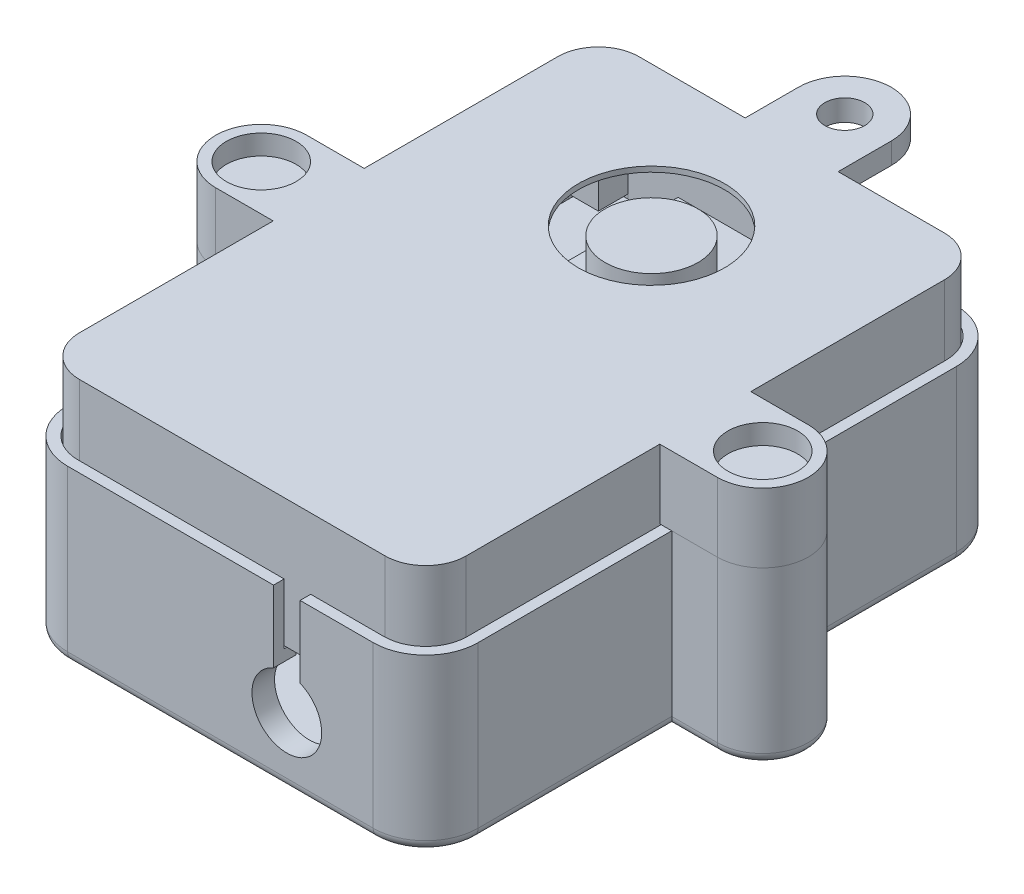
SolidWorks part; units mm, degrees
other "ESP32 Cam"
other "Front Lid"
other "Rear Lid"
ref_plane "Front Plane" through (0, 0, 0) normal (0, 0, 1) x (1, 0, 0)
ref_plane "Top Plane" through (0, 0, 0) normal (0, 1, 0) x (1, 0, 0)
ref_plane "Right Plane" through (0, 0, 0) normal (1, 0, 0) x (0, 0, -1)
sketch "Sketch1" plane through (0, 0, 0) normal (0, 1, 0) x (1, 0, 0)
  line L1 (-11.5, 20) -> (11.5, 20)
  line L2 (-13.5, 18) -> (-13.5, -18)
  line L3 (-11.5, -20) -> (11.5, -20)
  line L4 (13.5, 18) -> (13.5, -18)
  line L5 (-13.5, 20) -> (13.5, -20) construction
  line L6 (-13.5, -20) -> (13.5, 20) construction
  arc A0 (-11.5, 20) -> (-13.5, 18) centre (-11.5, 18) ccw
  arc A1 (11.5, 20) -> (13.5, 18) centre (11.5, 18) cw
  arc A2 (11.5, -20) -> (13.5, -18) centre (11.5, -18) ccw
  arc A3 (-13.5, -18) -> (-11.5, -20) centre (-11.5, -18) ccw
  point P0 (0, 0)
  dimension "D3" = 2
  dimension "D1" = 27
  dimension "D2" = 40
extrude "Boss-Extrude1" add sketch "Sketch1" along normal blind 1
sketch "Sketch2" plane through (0, 1, 0) normal (0, 1, 0) x (1, 0, 0)
  line L0 (0, 0) -> (0, 20) construction
  line L1 (11.5, 20) -> (-11.5, 20) construction
  line L3 (-7.5, 20) -> (7.5, 20)
  line L4 (-7.5, 20) -> (-7.5, 5)
  line L5 (-7.5, 5) -> (7.5, 5)
  line L6 (7.5, 20) -> (7.5, 5)
  line L7 (-7.5, 20) -> (7.5, 5) construction
  line L8 (-7.5, 5) -> (7.5, 20) construction
  point P5 (0, 12.5)
  dimension "D1" = 15
extrude "Boss-Extrude2" add sketch "Sketch2" along normal blind 2
sketch "Sketch3" plane through (0, 3, 0) normal (0, 1, 0) x (1, 0, 0)
  line L0 (0, 5) -> (0, 20) construction
  line L1 (-7.5, 5) -> (7.5, 5) construction
  line L2 (7.5, 20) -> (-7.5, 20) construction
  circle A0 centre (0, 10.5) radius 3.5
  dimension "D1" = 7
  dimension "D2" = 5.5
extrude "Lens Position" add sketch "Sketch3" along normal blind 6
sketch "Sketch5" plane through (0, 1, 0) normal (0, 1, 0) x (1, 0, 0)
  line L0 (-11.5, -20) -> (11.5, -20) construction
  line L1 (10, -8) -> (13, -8)
  line L2 (10, -8) -> (10, -11)
  line L3 (10, -11) -> (13, -11)
  line L4 (13, -8) -> (13, -11)
  line L5 (10, -8) -> (13, -11) construction
  line L6 (10, -11) -> (13, -8) construction
  line L7 (13.5, -18) -> (13.5, 18) construction
  point P0 (11.5, -9.5)
  dimension "D1" = 3
  dimension "D2" = 10.5
  dimension "D3" = 2
extrude "Boss-Extrude4" add sketch "Sketch5" along normal blind 1
sketch "Sketch6" plane through (0, 9, 0) normal (0, 1, 0) x (1, 0, 0)
  line L37 (7.5, 21.05) -> (-7.5, 21.05)
  line L38 (-7.5, 21.05) -> (-11.5, 21.05)
  line L39 (-14.55, 18) -> (-14.55, -18)
  line L40 (-11.5, -21.05) -> (11.5, -21.05)
  line L41 (14.55, -18) -> (14.55, 18)
  line L42 (11.5, 21.05) -> (7.5, 21.05)
  line L43 (7.5, 20.25) -> (-7.5, 20.25)
  line L44 (11.5, 20.25) -> (7.5, 20.25)
  line L45 (13.75, -18) -> (13.75, 18)
  line L46 (-11.5, -20.25) -> (11.5, -20.25)
  line L47 (-13.75, 18) -> (-13.75, -18)
  line L48 (-7.5, 20.25) -> (-11.5, 20.25)
  line L55 (7.5, 20.25) -> (-7.5, 20.25) construction
  line L56 (11.5, 20.25) -> (7.5, 20.25) construction
  line L57 (13.75, -18) -> (13.75, 18) construction
  line L58 (-11.5, -20.25) -> (11.5, -20.25) construction
  line L59 (-13.75, 18) -> (-13.75, -18) construction
  line L60 (-7.5, 20.25) -> (-11.5, 20.25) construction
  circle A6 centre (0, 10.5) radius 5.5
  circle A8 centre (0, 10.5) radius 5.5
  arc A36 (-11.5, 21.05) -> (-14.55, 18) centre (-11.5, 18) ccw
  arc A37 (-14.55, -18) -> (-11.5, -21.05) centre (-11.5, -18) ccw
  arc A38 (11.5, -21.05) -> (14.55, -18) centre (11.5, -18) ccw
  arc A39 (14.55, 18) -> (11.5, 21.05) centre (11.5, 18) ccw
  arc A40 (13.75, 18) -> (11.5, 20.25) centre (11.5, 18) ccw
  arc A41 (11.5, -20.25) -> (13.75, -18) centre (11.5, -18) ccw
  arc A42 (-13.75, -18) -> (-11.5, -20.25) centre (-11.5, -18) ccw
  arc A43 (-11.5, 20.25) -> (-13.75, 18) centre (-11.5, 18) ccw
  arc A44 (13.75, 18) -> (11.5, 20.25) centre (11.5, 18) ccw construction
  arc A45 (11.5, -20.25) -> (13.75, -18) centre (11.5, -18) ccw construction
  arc A46 (-13.75, -18) -> (-11.5, -20.25) centre (-11.5, -18) ccw construction
  arc A47 (-11.5, 20.25) -> (-13.75, 18) centre (-11.5, 18) ccw construction
  dimension "D1" = 0.25
  dimension "D2" = 0.8
  dimension "D3" = 2
extrude "Lens Opening" add sketch "Sketch6" along normal blind 0.4 from offset 0.25 separate body
sketch "Sketch8" plane through (0, 9.25, 0) normal (0, -1, 0) x (1, 0, 0)
  line L4 (-11.5, -21.05) -> (11.5, -21.05)
  line L5 (14.55, -18) -> (14.55, 18)
  line L6 (11.5, 21.05) -> (-11.5, 21.05)
  line L7 (-14.55, 18) -> (-14.55, -18)
  line L8 (-11.5, -21.05) -> (11.5, -21.05)
  line L9 (14.55, -18) -> (14.55, 18)
  line L10 (11.5, 21.05) -> (-11.5, 21.05)
  line L11 (-14.55, 18) -> (-14.55, -18)
  line L16 (-11.5, -20.25) -> (11.5, -20.25)
  line L17 (13.75, -18) -> (13.75, 18)
  line L18 (11.5, 20.25) -> (-11.5, 20.25)
  line L19 (-13.75, 18) -> (-13.75, -18)
  line L20 (-11.5, -20.25) -> (11.5, -20.25)
  line L21 (13.75, -18) -> (13.75, 18)
  line L22 (11.5, 20.25) -> (-11.5, 20.25)
  line L23 (-13.75, 18) -> (-13.75, -18)
  arc A4 (11.5, -21.05) -> (14.55, -18) centre (11.5, -18) ccw
  arc A5 (14.55, 18) -> (11.5, 21.05) centre (11.5, 18) ccw
  arc A6 (-11.5, 21.05) -> (-14.55, 18) centre (-11.5, 18) ccw
  arc A7 (-14.55, -18) -> (-11.5, -21.05) centre (-11.5, -18) ccw
  arc A8 (11.5, -21.05) -> (14.55, -18) centre (11.5, -18) ccw
  arc A9 (14.55, 18) -> (11.5, 21.05) centre (11.5, 18) ccw
  arc A10 (-11.5, 21.05) -> (-14.55, 18) centre (-11.5, 18) ccw
  arc A11 (-14.55, -18) -> (-11.5, -21.05) centre (-11.5, -18) ccw
  arc A16 (11.5, -20.25) -> (13.75, -18) centre (11.5, -18) ccw
  arc A17 (13.75, 18) -> (11.5, 20.25) centre (11.5, 18) ccw
  arc A18 (-11.5, 20.25) -> (-13.75, 18) centre (-11.5, 18) ccw
  arc A19 (-13.75, -18) -> (-11.5, -20.25) centre (-11.5, -18) ccw
  arc A20 (11.5, -20.25) -> (13.75, -18) centre (11.5, -18) ccw
  arc A21 (13.75, 18) -> (11.5, 20.25) centre (11.5, 18) ccw
  arc A22 (-11.5, 20.25) -> (-13.75, 18) centre (-11.5, 18) ccw
  arc A23 (-13.75, -18) -> (-11.5, -20.25) centre (-11.5, -18) ccw
  dimension "D1" = 0
  dimension "D2" = 0.8
extrude "Boss-Extrude7" add sketch "Sketch8" along normal up to vertex (9.25 mm away) up to point (-11.5, 0, 20)
sketch "Sketch9" plane through (0, 9.25, 0) normal (0, -1, 0) x (1, 0, 0)
  line L0 (13.75, 18) -> (11.5, 18)
  line L1 (11.5, 18) -> (11.5, 20.25)
  line L2 (4.95, 0) -> (-4.95, 0) construction
  line L3 (11.5, -18) -> (11.5, -20.25)
  line L4 (13.75, -18) -> (11.5, -18)
  line L5 (0, -4.95) -> (0, 4.95) construction
  line L6 (-13.75, -18) -> (-11.5, -18)
  line L7 (-11.5, -18) -> (-11.5, -20.25)
  line L8 (-11.5, 18) -> (-11.5, 20.25)
  line L9 (-13.75, 18) -> (-11.5, 18)
  arc A0 (13.75, 18) -> (11.5, 20.25) centre (11.5, 18) ccw construction
  arc A1 (13.75, 18) -> (11.5, 20.25) centre (11.5, 18) ccw
  arc A2 (13.75, -18) -> (11.5, -20.25) centre (11.5, -18) cw
  arc A3 (-13.75, -18) -> (-11.5, -20.25) centre (-11.5, -18) ccw
  arc A4 (-13.75, 18) -> (-11.5, 20.25) centre (-11.5, 18) cw
extrude "Boss-Extrude9" add sketch "Sketch9" along normal offset from surface (8.15 mm away) 0.1 up to face at (0, 1, -4.1667)
sketch "Sketch11" plane through (0, 9.65, 0) normal (0, 1, 0) x (1, 0, 0)
  line L1 (13.75, -7.6) -> (9.6, -7.6)
  line L2 (9.6, -7.6) -> (9.6, -11.4)
  line L3 (9.6, -11.4) -> (13.75, -11.4)
  line L4 (13, -11) -> (13, -8)
  line L5 (13, -8) -> (10, -8)
  line L6 (10, -8) -> (10, -11)
  line L7 (10, -11) -> (13, -11)
  line L8 (13, -11) -> (13, -8) construction
  line L9 (13, -8) -> (10, -8) construction
  line L10 (10, -8) -> (10, -11) construction
  line L11 (10, -11) -> (13, -11) construction
  line L12 (13.75, 18) -> (13.75, -18) construction
  line L13 (13.75, -7.6) -> (13.75, -11.4)
  line L14 (9.6, -11.4) -> (13.4, -11.4) construction
  line L15 (13.4, -11.4) -> (13.4, -7.6) construction
  line L16 (13.4, -7.6) -> (9.6, -7.6) construction
  dimension "D1" = 0
  dimension "D2" = 0.4
extrude "Cut-Extrude1" [suppressed] cut sketch "Sketch11" against normal up to vertex
sketch "Sketch12" plane through (0, 0, 0) normal (0, -1, 0) x (1, 0, 0)
  line L0 (0, 0) -> (0, 20) construction
  line L1 (-11.5, 20) -> (11.5, 20) construction
  line L3 (9.375, -5.65) -> (-9.375, -5.65)
  line L4 (9.375, -5.65) -> (9.375, 20)
  line L5 (9.375, 20) -> (-9.375, 20)
  line L6 (-9.375, -5.65) -> (-9.375, 20)
  line L7 (9.375, -5.65) -> (-9.375, 20) construction
  line L8 (9.375, 20) -> (-9.375, -5.65) construction
  point P5 (0, 7.175)
  dimension "D1" = 18.75
  dimension "D2" = 25.65
extrude "Boss-Extrude10" add sketch "Sketch12" along normal blind 0.75
sketch "Sketch13" plane through (0, -0.75, 0) normal (0, -1, 0) x (1, 0, 0)
  line L0 (0, -5.65) -> (0, 20) construction
  line L1 (-9.375, -5.65) -> (9.375, -5.65) construction
  line L2 (8, 12.35) -> (2, 12.35) construction
  line L3 (2, 12.35) -> (-8, 12.35)
  line L4 (8, 9.35) -> (8, -5.15)
  line L5 (8, -5.15) -> (-8, -5.15)
  line L6 (-8, 12.35) -> (-8, -5.15)
  line L7 (8, 12.35) -> (-8, -5.15) construction
  line L8 (8, -5.15) -> (-8, 12.35) construction
  line L11 (8, 9.35) -> (2, 9.35)
  line L12 (2, 12.35) -> (2, 9.35)
  line L13 (8, 12.35) -> (8, 9.35) construction
  line L14 (9.375, 20) -> (11.5, 20) construction
  point P5 (0, 3.6)
  dimension "D1" = 16
  dimension "D2" = 17.5
  dimension "D3" = 3
  dimension "D4" = 6
  dimension "D5" = 0.5
extrude "Boss-Extrude11" add sketch "Sketch13" along normal blind 2.3
sketch "Sketch14" plane through (0, 0, 0) normal (0, -1, 0) x (1, 0, 0)
  line L0 (9.375, 20) -> (11.5, 20) construction
  line L1 (12.75, -16.2) -> (10.25, -16.2)
  line L2 (12.75, -16.2) -> (12.75, 4)
  line L3 (12.75, 4) -> (10.25, 4)
  line L4 (10.25, -16.2) -> (10.25, 4)
  line L5 (12.75, -16.2) -> (10.25, 4) construction
  line L6 (12.75, 4) -> (10.25, -16.2) construction
  line L7 (13.5, 18) -> (13.5, -18) construction
  point P0 (11.5, -6.1)
  dimension "D1" = 20.2
  dimension "D2" = 2.5
  dimension "D3" = 16
  dimension "D4" = 0.75
extrude "Boss-Extrude12" add sketch "Sketch14" along normal blind 2.45
sketch "Sketch16" plane through (0, -2.45, 0) normal (0, -1, 0) x (1, 0, 0)
  line L0 (11.5, 4) -> (11.5, -16.2) construction
  line L3 (11.2, 3) -> (11.8, 3)
  line L8 (11.2, 3) -> (11.2, 2.4)
  line L9 (11.2, 2.4) -> (11.8, 2.4)
  line L10 (11.8, 3) -> (11.8, 2.4)
  line L11 (12.75, 4) -> (10.25, 4) construction
  line L12 (10.25, -16.2) -> (12.75, -16.2) construction
  dimension "D1" = 0.6
  dimension "D2" = 1
extrude "Boss-Extrude14" add sketch "Sketch16" along normal blind 5.5
pattern_linear "LPattern1" count 8 spacing 2.5 along (0, 0, -1) of "Boss-Extrude14"
sketch "Sketch17" plane through (0, -3.05, 0) normal (0, -1, 0) x (1, 0, 0)
  line L14 (-11.5, -21.95) -> (11.5, -21.95)
  line L15 (15.45, -18) -> (15.45, 18)
  line L16 (-11.5, -21.15) -> (11.5, -21.15)
  line L17 (-14.65, 18) -> (-14.65, -18)
  line L18 (11.5, 21.15) -> (-11.5, 21.15)
  line L19 (-11.5, -21.15) -> (11.5, -21.15)
  line L20 (-14.65, 18) -> (-14.65, -18)
  line L21 (11.5, 21.15) -> (-11.5, 21.15)
  line L22 (14.65, -18) -> (14.65, 18)
  line L23 (11.5, 21.95) -> (-11.5, 21.95)
  line L24 (-15.45, 18) -> (-15.45, -18)
  arc A16 (11.5, -21.95) -> (15.45, -18) centre (11.5, -18) ccw
  arc A17 (15.45, 18) -> (11.5, 21.95) centre (11.5, 18) ccw
  arc A18 (-11.5, 21.95) -> (-15.45, 18) centre (-11.5, 18) ccw
  arc A19 (-15.45, -18) -> (-11.5, -21.95) centre (-11.5, -18) ccw
  arc A20 (11.5, -21.15) -> (14.65, -18) centre (11.5, -18) ccw
  arc A21 (-14.65, -18) -> (-11.5, -21.15) centre (-11.5, -18) ccw
  arc A22 (-11.5, 21.15) -> (-14.65, 18) centre (-11.5, 18) ccw
  arc A23 (14.65, 18) -> (11.5, 21.15) centre (11.5, 18) ccw
  arc A24 (11.5, -21.15) -> (14.65, -18) centre (11.5, -18) ccw
  arc A25 (-14.65, -18) -> (-11.5, -21.15) centre (-11.5, -18) ccw
  arc A26 (-11.5, 21.15) -> (-14.65, 18) centre (-11.5, 18) ccw
  arc A27 (14.65, 18) -> (11.5, 21.15) centre (11.5, 18) ccw
  dimension "D1" = 0.1
  dimension "D2" = 0.8
extrude "Boss-Extrude15" add sketch "Sketch17" against normal blind 12.5 from offset 5 separate body
sketch "Sketch18" plane through (0, -8.05, 0) normal (0, -1, 0) x (1, 0, 0)
  line L0 (-11.5, -20.25) -> (11.5, -20.25) construction
  line L1 (-13.75, 18) -> (-13.75, -18) construction
  line L2 (13.75, -18) -> (13.75, 18) construction
  line L3 (11.5, 20.25) -> (-11.5, 20.25) construction
  line L4 (-11.5, -20.25) -> (11.5, -20.25)
  line L5 (-13.75, 18) -> (-13.75, -18)
  line L6 (13.75, -18) -> (13.75, 18)
  line L7 (11.5, 20.25) -> (-11.5, 20.25)
  line L8 (-11.5, -21.15) -> (11.5, -21.15) construction
  line L9 (-14.65, 18) -> (-14.65, -18) construction
  line L10 (11.5, 21.15) -> (-11.5, 21.15) construction
  line L11 (14.65, -18) -> (14.65, 18) construction
  line L12 (-11.5, -21.15) -> (11.5, -21.15)
  line L13 (-14.65, 18) -> (-14.65, -18)
  line L14 (11.5, 21.15) -> (-11.5, 21.15)
  line L15 (14.65, -18) -> (14.65, 18)
  arc A0 (11.5, -20.25) -> (13.75, -18) centre (11.5, -18) ccw construction
  arc A1 (-13.75, -18) -> (-11.5, -20.25) centre (-11.5, -18) ccw construction
  arc A2 (-11.5, 20.25) -> (-13.75, 18) centre (-11.5, 18) ccw construction
  arc A3 (13.75, 18) -> (11.5, 20.25) centre (11.5, 18) ccw construction
  arc A4 (11.5, -20.25) -> (13.75, -18) centre (11.5, -18) ccw
  arc A5 (-13.75, -18) -> (-11.5, -20.25) centre (-11.5, -18) ccw
  arc A6 (-11.5, 20.25) -> (-13.75, 18) centre (-11.5, 18) ccw
  arc A7 (13.75, 18) -> (11.5, 20.25) centre (11.5, 18) ccw
  arc A8 (11.5, -21.15) -> (14.65, -18) centre (11.5, -18) ccw construction
  arc A9 (-14.65, -18) -> (-11.5, -21.15) centre (-11.5, -18) ccw construction
  arc A10 (-11.5, 21.15) -> (-14.65, 18) centre (-11.5, 18) ccw construction
  arc A11 (14.65, 18) -> (11.5, 21.15) centre (11.5, 18) ccw construction
  arc A12 (11.5, -21.15) -> (14.65, -18) centre (11.5, -18) ccw
  arc A13 (-14.65, -18) -> (-11.5, -21.15) centre (-11.5, -18) ccw
  arc A14 (-11.5, 21.15) -> (-14.65, 18) centre (-11.5, 18) ccw
  arc A15 (14.65, 18) -> (11.5, 21.15) centre (11.5, 18) ccw
extrude "Boss-Extrude16" add sketch "Sketch18" against normal offset from surface (7.95 mm away) 0.1 up to face at (0, 0, 0)
sketch "Sketch19" plane through (0, -8.05, 0) normal (0, -1, 0) x (1, 0, 0)
  line L165 (0, -9.955) -> (0, 9.955) construction
  line L166 (-13.25, -16.7) -> (-13.25, 4.5)
  line L167 (-13.25, 4.5) -> (-9.75, 4.5)
  line L168 (-9.75, 4.5) -> (-9.75, -16.7)
  line L169 (13.25, 4.5) -> (9.75, 4.5)
  line L170 (13.25, -16.7) -> (13.25, 4.5)
  line L171 (9.75, -16.7) -> (13.25, -16.7)
  line L172 (9.75, 4.5) -> (9.75, -16.7)
  line L173 (13.25, 4.5) -> (9.75, 4.5)
  line L174 (13.25, -16.7) -> (13.25, 4.5)
  line L175 (9.75, -16.7) -> (13.25, -16.7)
  line L176 (9.75, 4.5) -> (9.75, -16.7)
  line L177 (-9.75, -16.7) -> (-13.25, -16.7)
  line L178 (11.5, 21.95) -> (-11.5, 21.95) construction
  line L179 (-15.45, 18) -> (-15.45, -18) construction
  line L180 (-11.5, -21.95) -> (11.5, -21.95) construction
  line L181 (15.45, -18) -> (15.45, 18) construction
  line L182 (11.5, 21.95) -> (-11.5, 21.95)
  line L183 (-15.45, 18) -> (-15.45, -18)
  line L184 (-11.5, -21.95) -> (11.5, -21.95)
  line L185 (15.45, -18) -> (15.45, 18)
  arc A0 (15.45, 18) -> (11.5, 21.95) centre (11.5, 18) ccw construction
  arc A1 (-11.5, 21.95) -> (-15.45, 18) centre (-11.5, 18) ccw construction
  arc A2 (-15.45, -18) -> (-11.5, -21.95) centre (-11.5, -18) ccw construction
  arc A3 (11.5, -21.95) -> (15.45, -18) centre (11.5, -18) ccw construction
  arc A4 (15.45, 18) -> (11.5, 21.95) centre (11.5, 18) ccw
  arc A5 (-11.5, 21.95) -> (-15.45, 18) centre (-11.5, 18) ccw
  arc A6 (-15.45, -18) -> (-11.5, -21.95) centre (-11.5, -18) ccw
  arc A7 (11.5, -21.95) -> (15.45, -18) centre (11.5, -18) ccw
  dimension "D1" = 0.5
extrude "Boss-Extrude17" add sketch "Sketch19" along normal blind 0.4
sketch "Sketch20" plane through (0, 0, 21.95) normal (0, 0, 1) x (1, 0, 0)
  line L0 (2, -3.05) -> (2, -0.75) construction
  line L1 (8, -0.75) -> (2, -0.75) construction
  line L2 (8, -3.05) -> (8, -0.75) construction
  line L3 (8, -3.05) -> (2, -3.05) construction
  line L4 (2, -3.05) -> (2, -0.75) construction
  line L5 (8, -0.75) -> (2, -0.75) construction
  line L6 (8, -3.05) -> (8, -0.75) construction
  line L7 (8, -3.05) -> (2, -3.05) construction
  line L8 (8, -3.05) -> (2, -0.75) construction
  line L9 (8, -0.75) -> (2, -3.05) construction
  line L10 (5, -1.9) -> (5, -3.375) construction
  line L12 (9.375, -0.75) -> (-9.375, -0.75) construction
  line L13 (9.375, -0.75) -> (-9.375, -0.75) construction
  circle A0 centre (5, -3.375) radius 2.625
  dimension "D1" = 5.25
extrude "Cut-Extrude2" cut sketch "Sketch20" against normal up to next (1.7 mm away) contours A0
sketch "Sketch22" plane through (0, -8.05, 0) normal (0, 1, 0) x (1, 0, 0)
  line L0 (13.75, -18) -> (11.5, -18)
  line L1 (11.5, -18) -> (11.5, -20.25)
  line L2 (-9.955, 0) -> (9.955, 0) construction
  line L3 (11.5, 18) -> (11.5, 20.25)
  line L4 (13.75, 18) -> (11.5, 18)
  line L5 (0, -9.955) -> (0, 9.955) construction
  line L6 (-13.75, 18) -> (-11.5, 18)
  line L7 (-11.5, 18) -> (-11.5, 20.25)
  line L8 (-11.5, -18) -> (-11.5, -20.25)
  line L9 (-13.75, -18) -> (-11.5, -18)
  arc A0 (11.5, -20.25) -> (13.75, -18) centre (11.5, -18) ccw construction
  arc A1 (11.5, -20.25) -> (13.75, -18) centre (11.5, -18) ccw
  arc A2 (11.5, 20.25) -> (13.75, 18) centre (11.5, 18) cw
  arc A3 (-11.5, 20.25) -> (-13.75, 18) centre (-11.5, 18) ccw
  arc A4 (-11.5, -20.25) -> (-13.75, -18) centre (-11.5, -18) cw
extrude "Boss-Extrude18" add sketch "Sketch22" along normal up to vertex (6.05 mm away)
sketch "Sketch23" [suppressed] plane through (0, 9.25, 0) normal (0, -1, 0) x (1, 0, 0)
  line L1 (9.6, 11.4) -> (13.75, 11.4) construction
  line L2 (9.6, 7.6) -> (9.6, 11.4) construction
  line L3 (13.75, 7.6) -> (9.6, 7.6) construction
  line L5 (9.6, 11.4) -> (13.75, 11.4)
  line L6 (9.6, 7.6) -> (9.6, 11.4)
  line L7 (13.75, 7.6) -> (9.6, 7.6)
  line L8 (13.75, 6.8) -> (8.8, 6.8)
  line L9 (8.8, 6.8) -> (8.8, 12.2)
  line L10 (8.8, 12.2) -> (13.75, 12.2)
  line L11 (13.75, 7.6) -> (13.75, 6.8)
  line L12 (13.75, 12.2) -> (13.75, 11.4)
  dimension "D1" = 0.8
extrude "Boss-Extrude19" [suppressed] add sketch "Sketch23" along normal offset from surface (7.15 mm away) 1
mirror "Mirror1" about plane through (0, 0, 0) normal (1, 0, 0) of "LPattern1", "Boss-Extrude12", "Boss-Extrude14"
sketch "Sketch24" plane through (0, 9.65, 0) normal (0, 1, 0) x (1, 0, 0)
  line L0 (0, 0) -> (0, 25.05) construction
  line L2 (-3.5, 25.05) -> (-3.5, 21.05)
  line L8 (11.5, 21.05) -> (-11.5, 21.05) construction
  line L9 (3.5, 25.05) -> (3.5, 21.05)
  line L10 (-3.5, 21.05) -> (3.5, 21.05)
  circle A1 centre (0, 25.05) radius 1.5
  arc A2 (3.5, 25.05) -> (-3.5, 25.05) centre (0, 25.05) ccw
  circle A3 centre (0, 25.05) radius 3.5 construction
  dimension "D2" = 3
  dimension "D1" = 2
extrude "Boss-Extrude20" add sketch "Sketch24" against normal blind 1.6
sketch "Sketch25" plane through (0, -8.45, 0) normal (0, -1, 0) x (1, 0, 0)
  line L0 (15.45, 0) -> (18.875, 0) construction
  line L1 (15.45, -18) -> (15.45, 18) construction
  line L2 (18.875, 3.425) -> (15.45, 3.425)
  line L3 (18.875, -3.425) -> (15.45, -3.425)
  line L4 (15.45, -3.425) -> (15.45, 0)
  line L5 (15.45, 0) -> (15.45, 3.425)
  line L6 (0, -9.955) -> (0, 9.955) construction
  line L7 (-15.45, 0) -> (-18.875, 0) construction
  line L8 (-15.45, 0) -> (-15.45, 3.425)
  line L9 (-15.45, -3.425) -> (-15.45, 0)
  line L10 (-18.875, -3.425) -> (-15.45, -3.425)
  line L11 (-18.875, 3.425) -> (-15.45, 3.425)
  circle A0 centre (18.875, 0) radius 2.625 construction
  arc A1 (18.875, -3.425) -> (18.875, 3.425) centre (18.875, 0) ccw
  circle A2 centre (18.875, 0) radius 3.425 construction
  circle A3 centre (-18.875, 0) radius 2.625 construction
  arc A4 (-18.875, -3.425) -> (-18.875, 3.425) centre (-18.875, 0) cw
  dimension "D1" = 5.25
  dimension "D2" = 0.8
extrude "Boss-Extrude21" add sketch "Sketch25" against normal up to vertex (12.9 mm away) up to point (15.45, 4.45, 18)
sketch "Sketch26" plane through (0, 9.65, 0) normal (0, 1, 0) x (1, 0, 0)
  line L0 (15.45, 3.425) -> (18.875, 3.425) construction
  line L1 (18.875, -3.425) -> (15.45, -3.425) construction
  line L2 (15.45, 3.425) -> (18.875, 3.425)
  line L3 (18.875, -3.425) -> (15.45, -3.425)
  line L4 (15.45, 3.425) -> (14.55, 3.425)
  line L5 (14.55, -18) -> (14.55, 18) construction
  line L6 (14.55, 3.425) -> (14.55, -3.425)
  line L7 (14.55, -3.425) -> (15.45, -3.425)
  line L8 (0, -9.955) -> (0, 9.955) construction
  line L9 (-14.55, -3.425) -> (-15.45, -3.425)
  line L10 (-14.55, 3.425) -> (-14.55, -3.425)
  line L11 (-15.45, 3.425) -> (-14.55, 3.425)
  line L12 (-18.875, -3.425) -> (-15.45, -3.425)
  line L13 (-15.45, 3.425) -> (-18.875, 3.425)
  arc A0 (18.875, -3.425) -> (18.875, 3.425) centre (18.875, 0) ccw construction
  arc A1 (18.875, -3.425) -> (18.875, 3.425) centre (18.875, 0) ccw
  arc A2 (-18.875, -3.425) -> (-18.875, 3.425) centre (-18.875, 0) cw
extrude "Boss-Extrude22" add sketch "Sketch26" against normal up to vertex (5.2 mm away)
sketch "Sketch27" plane through (0, 4.45, 0) normal (0, 1, 0) x (1, 0, 0)
  line L0 (0, -9.955) -> (0, 9.955) construction
  circle A0 centre (18.875, 0) radius 2.625 construction
  circle A1 centre (18.875, 0) radius 2.625
  circle A2 centre (-18.875, 0) radius 2.625
extrude "Magnet Hole" cut sketch "Sketch27" against normal mid plane 2.5
sketch "Sketch28" plane through (0, 9.65, 0) normal (0, 1, 0) x (1, 0, 0)
  line L0 (0, -9.955) -> (0, 9.955) construction
  circle A0 centre (18.875, 0) radius 2.625 construction
  circle A1 centre (18.875, 0) radius 2.625
  circle A2 centre (-18.875, 0) radius 2.625
extrude "Cut-Extrude3" cut sketch "Sketch28" against normal blind 1.5
sketch "Sketch29" plane through (0, -8.45, 0) normal (0, -1, 0) x (1, 0, 0)
  line L0 (0, -9.955) -> (0, 9.955) construction
  circle A0 centre (18.875, 0) radius 2.625 construction
  circle A1 centre (18.875, 0) radius 2.625
  circle A2 centre (-18.875, 0) radius 2.625
extrude "Cut-Extrude4" cut sketch "Sketch29" against normal blind 1.5
fillet "Fillet2" radius 0.8 16 edges at (-14.2931, -8.45, -20.7931) (-15.45, -8.45, 10.7125) (-15.45, -8.45, -10.7125) (-14.2931, -8.45, 20.7931) (0, -8.45, 21.95) (14.2931, -8.45, 20.7931) (15.45, -8.45, -10.7125) (15.45, -8.45, 10.7125) (14.2931, -8.45, -20.7931) (0, -8.45, -21.95) (17.1625, -8.45, -3.425) (17.1625, -8.45, 3.425) (22.3, -8.45, 0) (-17.1625, -8.45, 3.425) (-17.1625, -8.45, -3.425) (-22.3, -8.45, 0)
sketch "Sketch30" plane through (0, 0, 21.95) normal (0, 0, 1) x (1, 0, 0)
  line L0 (5, -3.375) -> (5, 4.45) construction
  line L1 (11.5, 4.45) -> (-11.5, 4.45) construction
  line L2 (6, 4.45) -> (6, -0.9479)
  line L3 (4, 4.45) -> (4, -0.9479)
  line L4 (4, 4.45) -> (6, 4.45)
  circle A0 centre (5, -3.375) radius 2.625 construction
  arc A1 (6, -0.9479) -> (4, -0.9479) centre (5, -3.375) ccw
  dimension "D1" = 2
extrude "Cut-Extrude5" cut sketch "Sketch30" against normal up to next (1.7 mm away)
